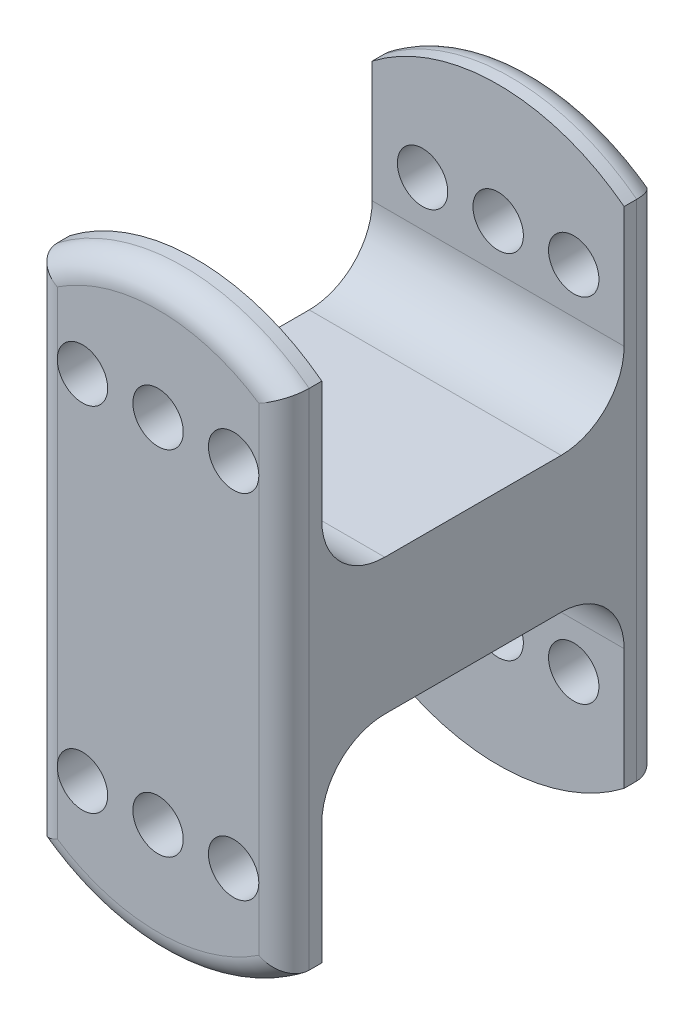
SolidWorks part; units mm, degrees
ref_plane "Front Plane" through (0, 0, 0) normal (0, 0, 1) x (1, 0, 0)
ref_plane "Top Plane" through (0, 0, 0) normal (0, 1, 0) x (1, 0, 0)
ref_plane "Right Plane" through (0, 0, 0) normal (1, 0, 0) x (0, 0, -1)
sketch "Sketch1" plane through (0, 0, 0) normal (0, 0, 1) x (1, 0, 0)
  line L0 (0, 0) -> (-10, -13.0323) construction
  line L1 (0, 0) -> (10, -13.0323) construction
  line L2 (-10, -13.0323) -> (10, -13.0323) construction
  line L3 (-10, -13.0323) -> (-10, 26.9677)
  line L5 (10, 26.9677) -> (10, -13.0323)
  line L6 (0, 13.9355) -> (10, 26.9677) construction
  line L7 (-10, 26.9677) -> (0, 13.9355) construction
  line L8 (-10, 26.9677) -> (10, 26.9677) construction
  line L9 (-10, 6.9677) -> (10, 6.9677) construction
  arc A0 (-10, -13.0323) -> (10, -13.0323) centre (0, 0) ccw
  arc A1 (-10, 26.9677) -> (10, 26.9677) centre (0, 13.9355) cw
  circle A2 centre (0, -7.0323) radius 2
  circle A3 centre (6, -7.0323) radius 2
  circle A4 centre (-6, -7.0323) radius 2
  circle A5 centre (6, 20.9677) radius 2
  circle A6 centre (0, 20.9677) radius 2
  circle A7 centre (-6, 20.9677) radius 2
  dimension "D6" = 4
  dimension "D7" = 4
  dimension "D10" = 4
  dimension "D1" = 75
  dimension "D2" = 20
  dimension "D3" = 75
  dimension "D4" = 40
  dimension "D5" = 6
  dimension "D8" = 6
  dimension "D9" = 6
extrude "Boss-Extrude1" add sketch "Sketch1" along normal blind 30
sketch "Sketch2" plane through (10, 0, 0) normal (1, 0, 0) x (0, 0, -1)
  line L0 (-30, -16.4268) -> (0, -16.4268) construction
  line L1 (-27, -16.4268) -> (-3, -16.4268)
  line L2 (-27, -16.4268) -> (-27, 1.5732)
  line L3 (-27, 1.5732) -> (-3, 1.5732)
  line L4 (-3, -16.4268) -> (-3, 1.5732)
  line L5 (-30, 6.9677) -> (0, 6.9677) construction
  line L6 (-30, -13.0323) -> (-30, 26.9677) construction
  line L7 (0, -13.0323) -> (0, 26.9677) construction
  line L8 (-27, 12.3623) -> (-3, 12.3623)
  line L9 (-3, 30.3623) -> (-3, 12.3623)
  line L10 (-27, 30.3623) -> (-3, 30.3623)
  line L11 (-27, 30.3623) -> (-27, 12.3623)
  dimension "D1" = 3
  dimension "D2" = 3
  dimension "D3" = 18
extrude "Cut-Extrude1" cut sketch "Sketch2" against normal through all
fillet "Fillet1" radius 5 4 edges at (0, 1.5732, 27) (0, 1.5732, 3) (0, 12.3623, 27) (0, 12.3623, 3)
fillet "Fillet2" radius 2 8 edges at (0, -16.4268, 30) (0, 30.3623, 30) (0, 30.3623, 0) (0, -16.4268, 0) (10, 6.9677, 0) (10, 6.9677, 30) (-10, 6.9677, 30) (-10, 6.9677, 0)
